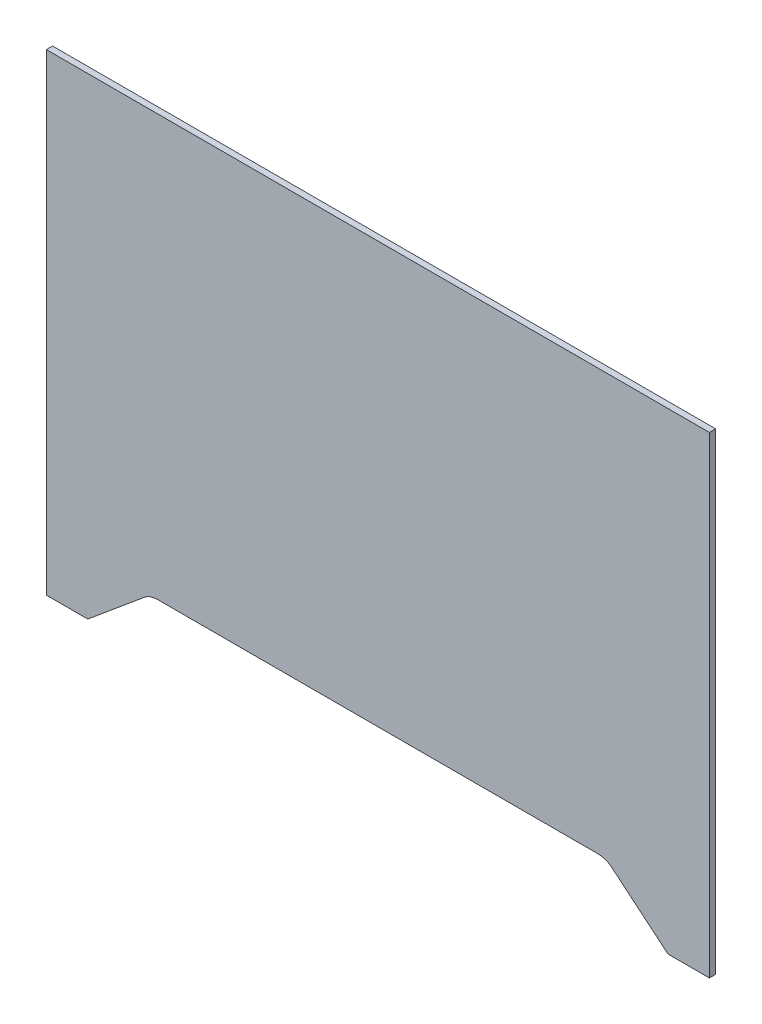
SolidWorks part; units mm, degrees
ref_plane "前视基准面" through (0, 0, 0) normal (0, 0, 1) x (1, 0, 0)
ref_plane "上视基准面" through (0, 0, 0) normal (0, 1, 0) x (1, 0, 0)
ref_plane "右视基准面" through (0, 0, 0) normal (1, 0, 0) x (0, 0, -1)
sketch "Sketch1" plane through (0, 0, 0) normal (0, 0, 1) x (1, 0, 0)
  line L0 (0, -114) -> (0, 0) construction
  line L1 (-160, -114) -> (160, -114) construction
  line L2 (-160, -114) -> (-160, 114)
  line L3 (-160, 114) -> (160, 114)
  line L4 (160, -114) -> (160, 114)
  line L5 (-160, -114) -> (160, 114) construction
  line L6 (-160, 114) -> (160, -114) construction
  line L7 (-106.3795, -89) -> (106.3795, -89)
  line L8 (112.7813, -91.3178) -> (140, -114)
  line L9 (140, -114) -> (160, -114)
  line L10 (-140, -114) -> (-160, -114)
  line L11 (-112.7813, -91.3178) -> (-140, -114)
  arc A0 (112.7813, -91.3178) -> (106.3795, -89) centre (106.3795, -99) ccw
  arc A1 (-112.7813, -91.3178) -> (-106.3795, -89) centre (-106.3795, -99) cw
  point P0 (0, 0)
  point P13 (110, -89)
  point P18 (0, -89)
  dimension "D6" = 10
  dimension "D1" = 320
  dimension "D2" = 228
  dimension "D3" = 25
  dimension "D4" = 20
  dimension "D5" = 110
extrude "Boss-Extrude1" add sketch "Sketch1" along normal blind 3
